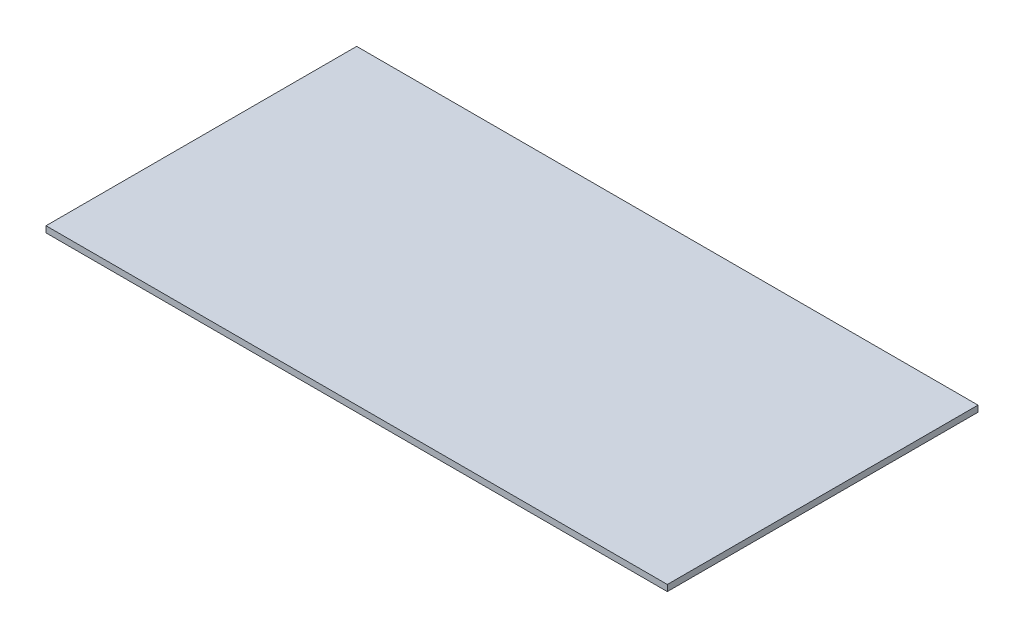
SolidWorks part; units mm, degrees
ref_plane "Front Plane" through (0, 0, 0) normal (0, 0, 1) x (1, 0, 0)
ref_plane "Top Plane" through (0, 0, 0) normal (0, 1, 0) x (1, 0, 0)
ref_plane "Right Plane" through (0, 0, 0) normal (1, 0, 0) x (0, 0, -1)
sketch "Sketch1" plane through (0, 0, 0) normal (0, 1, 0) x (1, 0, 0)
  line L1 (152.4, -76.2) -> (-152.4, -76.2)
  line L2 (152.4, -76.2) -> (152.4, 76.2)
  line L3 (152.4, 76.2) -> (-152.4, 76.2)
  line L4 (-152.4, -76.2) -> (-152.4, 76.2)
  line L5 (152.4, -76.2) -> (-152.4, 76.2) construction
  line L6 (152.4, 76.2) -> (-152.4, -76.2) construction
  point P0 (0, 0)
  dimension "D1" = 152.4
  dimension "D2" = 304.8
extrude "Boss-Extrude1" add sketch "Sketch1" along normal blind 3.048
